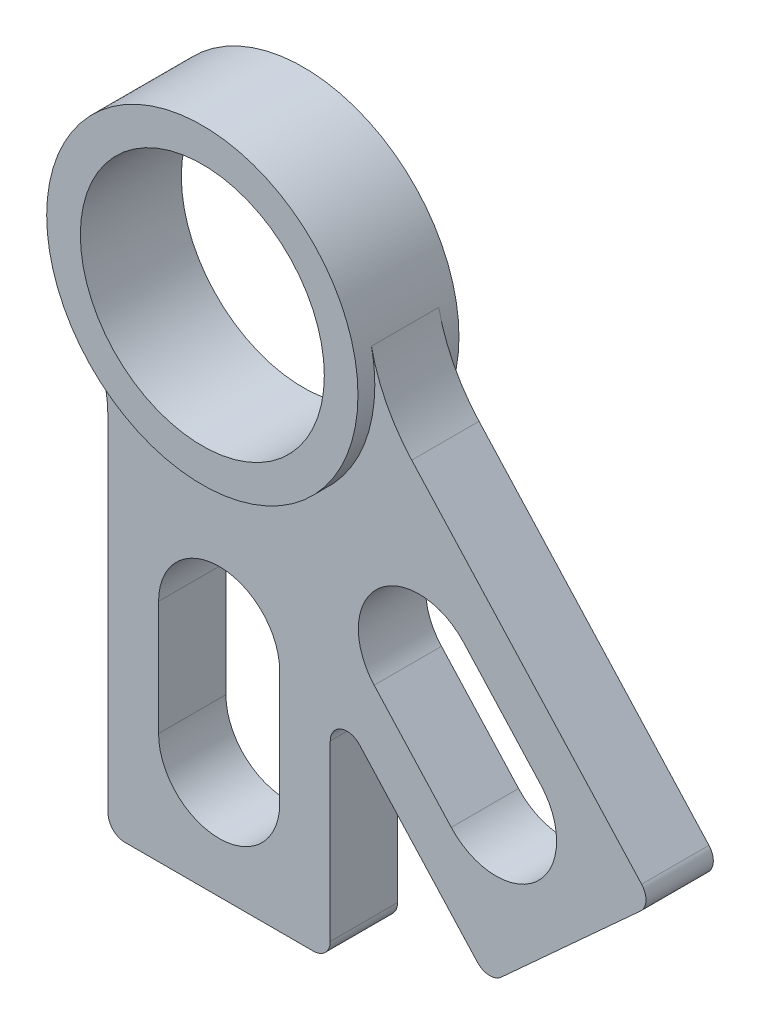
SolidWorks part; units mm, degrees
material "AISI 4130 Steel, annealed at 865C"
ref_plane "X-Y Datum" through (0, 0, 0) normal (0, 0, 1) x (1, 0, 0)
ref_plane "X-Z Datum" through (0, 0, 0) normal (0, 1, 0) x (1, 0, 0)
ref_plane "Y-Z Datum" through (0, 0, 0) normal (1, 0, 0) x (0, 0, -1)
sketch "Sketch1" plane through (0, 0, 0) normal (0, 0, 1) x (1, 0, 0)
  line L0 (0, -38.6445) -> (0, -27.8495) construction
  line L1 (-5.715, -38.6445) -> (-5.715, -27.8495)
  line L2 (5.715, -38.6445) -> (5.715, -27.8495)
  line L3 (26.1137, -28.6584) -> (18.843, -20.6791) construction
  line L4 (21.8894, -32.5076) -> (14.6186, -24.5283)
  line L5 (30.338, -24.8091) -> (23.0673, -16.8299)
  line L6 (-10.4775, -15.467) -> (-10.4775, -49.122)
  line L7 (-10.4775, -49.122) -> (10.4775, -49.122)
  line L10 (25.426, -43.4598) -> (40.9152, -29.346)
  line L11 (40.9152, -29.346) -> (18.162, -4.3757)
  line L12 (0, -38.6445) -> (0, 0) construction
  line L13 (0, 0) -> (26.1137, -28.6584) construction
  line L14 (0, -44.3595) -> (0, -49.122) construction
  line L15 (29.9629, -32.8827) -> (33.1706, -36.4029) construction
  line L16 (26.7026, -20.8195) -> (30.2229, -17.6118) construction
  line L17 (-5.715, -33.247) -> (-10.4775, -33.247) construction
  line L18 (-10.4775, -17.372) -> (10.4775, -17.372) construction
  line L19 (10.4775, -17.372) -> (10.4775, -49.122) construction
  line L20 (5.715, -33.247) -> (10.4775, -33.247) construction
  line L21 (0, -22.1345) -> (0, -17.372) construction
  line L22 (25.426, -43.4598) -> (4.0415, -19.9915) construction
  line L23 (4.0415, -19.9915) -> (19.5306, -5.8777) construction
  line L24 (18.254, -28.518) -> (14.7338, -31.7256) construction
  line L25 (14.9937, -16.4548) -> (11.7861, -12.9346) construction
  line L30 (25.426, -43.4598) -> (10.4775, -27.0546)
  line L32 (10.4775, -27.0546) -> (10.4775, -49.122)
  circle A0 centre (0, 0) radius 11.5062
  arc A1 (-5.715, -38.6445) -> (5.715, -38.6445) centre (0, -38.6445) ccw
  arc A2 (5.715, -27.8495) -> (-5.715, -27.8495) centre (0, -27.8495) ccw
  arc A3 (21.8894, -32.5076) -> (30.338, -24.8091) centre (26.1137, -28.6584) ccw
  arc A4 (23.0673, -16.8299) -> (14.6186, -24.5283) centre (18.843, -20.6791) ccw
  arc A5 (14.3641, 3.0349) -> (-12.6615, -7.4313) centre (0, 0) ccw
  arc A6 (18.162, -4.3757) -> (14.3641, 3.0349) centre (29.8962, 6.3166) cw
  arc A7 (-10.4775, -15.467) -> (-12.6615, -7.4313) centre (-26.3525, -15.467) ccw
  arc A14 (-12.6615, -7.4313) -> (14.3641, 3.0349) centre (0, 0) ccw
  point P5 (0, -33.247)
  point P11 (22.4783, -24.6687)
  point P24 (33.1706, -36.4029)
  point P31 (0, -49.122)
  point P39 (29.9629, -32.8827)
  dimension "D1" = 23.0124
  dimension "D2" = 14.6812
  dimension "D8" = 15.875
  dimension "D9" = 42.34
  dimension "D3" = 20.955
  dimension "D4" = 4.7625
  dimension "D5" = 31.75
  dimension "D6" = 2.032
  dimension "D7" = 1.905
extrude "Boss-Extrude1" add sketch "Sketch1" along normal mid plane 9.525 contours A14 A7 L6 L7 L32 L30 L10 L11 A6 A4 L5 A3 L4 A2 L2 A1 L1 | A5 A14 A0 region at (10.4972, -27.0002, 0) region at (-5.152, 13.3032, 0)
sketch "Sketch3" plane through (0, 0, 0) normal (0, 0, 1) x (1, 0, 0)
  line L0 (0, -38.6445) -> (0, -27.8495) construction
  line L1 (-5.715, -38.6445) -> (-5.715, -27.8495)
  line L2 (5.715, -38.6445) -> (5.715, -27.8495)
  line L3 (26.1137, -28.6584) -> (18.843, -20.6791) construction
  line L4 (21.8894, -32.5076) -> (14.6186, -24.5283)
  line L5 (30.338, -24.8091) -> (23.0673, -16.8299)
  line L6 (-10.4775, -15.467) -> (-10.4775, -49.122)
  line L7 (-10.4775, -49.122) -> (10.4775, -49.122)
  line L10 (25.426, -43.4598) -> (40.9152, -29.346)
  line L11 (40.9152, -29.346) -> (18.162, -4.3757)
  line L12 (0, -38.6445) -> (0, 0) construction
  line L13 (0, 0) -> (26.1137, -28.6584) construction
  line L14 (0, -44.3595) -> (0, -49.122) construction
  line L15 (29.9629, -32.8827) -> (33.1706, -36.4029) construction
  line L16 (26.7026, -20.8195) -> (30.2229, -17.6118) construction
  line L17 (-5.715, -33.247) -> (-10.4775, -33.247) construction
  line L18 (-10.4775, -17.372) -> (10.4775, -17.372) construction
  line L19 (10.4775, -17.372) -> (10.4775, -49.122) construction
  line L20 (5.715, -33.247) -> (10.4775, -33.247) construction
  line L21 (0, -22.1345) -> (0, -17.372) construction
  line L22 (25.426, -43.4598) -> (4.0415, -19.9915) construction
  line L23 (4.0415, -19.9915) -> (19.5306, -5.8777) construction
  line L24 (18.254, -28.518) -> (14.7338, -31.7256) construction
  line L25 (14.9937, -16.4548) -> (11.7861, -12.9346) construction
  line L30 (25.426, -43.4598) -> (10.4775, -27.0546)
  line L32 (10.4775, -27.0546) -> (10.4775, -49.122)
  circle A0 centre (0, 0) radius 11.4954
  arc A1 (-5.715, -38.6445) -> (5.715, -38.6445) centre (0, -38.6445) ccw
  arc A2 (5.715, -27.8495) -> (-5.715, -27.8495) centre (0, -27.8495) ccw
  arc A3 (21.8894, -32.5076) -> (30.338, -24.8091) centre (26.1137, -28.6584) ccw
  arc A4 (23.0673, -16.8299) -> (14.6186, -24.5283) centre (18.843, -20.6791) ccw
  arc A5 (14.3641, 3.0349) -> (-12.6615, -7.4313) centre (0, 0) ccw
  arc A6 (18.162, -4.3757) -> (14.3641, 3.0349) centre (29.8962, 6.3166) cw
  arc A7 (-10.4775, -15.467) -> (-12.6615, -7.4313) centre (-26.3525, -15.467) ccw
  arc A14 (-12.6615, -7.4313) -> (14.3641, 3.0349) centre (0, 0) ccw
  point P5 (0, -33.247)
  point P11 (22.4783, -24.6687)
  point P24 (33.1706, -36.4029)
  point P31 (0, -49.122)
  point P39 (29.9629, -32.8827)
  dimension "D1" = 22.9908
  dimension "D2" = 14.6812
  dimension "D8" = 15.875
  dimension "D9" = 42.34
  dimension "D3" = 20.955
  dimension "D4" = 4.7625
  dimension "D5" = 31.75
  dimension "D6" = 2.032
  dimension "D7" = 1.905
extrude "Cut-Extrude1" cut sketch "Sketch3" against normal blind 1.5875 from surface contours A14 A7 L6 L7 L32 L30 L10 L11 A6 A4 L5 A3 L4 A2 L2 A1 L1 region at (10.4972, -27.0002, 0) starting at face at (8.8994, -22.9514, 4.7625)
extrude "Cut-Extrude2" cut sketch "Sketch3<11>" along normal blind 1.5875 from surface contours A14 A7 L6 L7 L32 L30 L10 L11 A6 A4 L5 A3 L4 A2 L2 A1 L1 region at (10.4972, -27.0002, 0) starting at face at (8.8994, -22.9514, -4.7625)
sketch "Sketch3<11>" plane through (0, 0, 0) normal (0, 0, 1) x (1, 0, 0) same geometry as "Sketch3"
fillet "Fillet1" radius 1.5875 5 edges at (40.9152, -29.346, 0) (25.426, -43.4598, 0) (10.4775, -27.0546, 0) (10.4775, -49.122, 0) (-10.4775, -49.122, 0)
